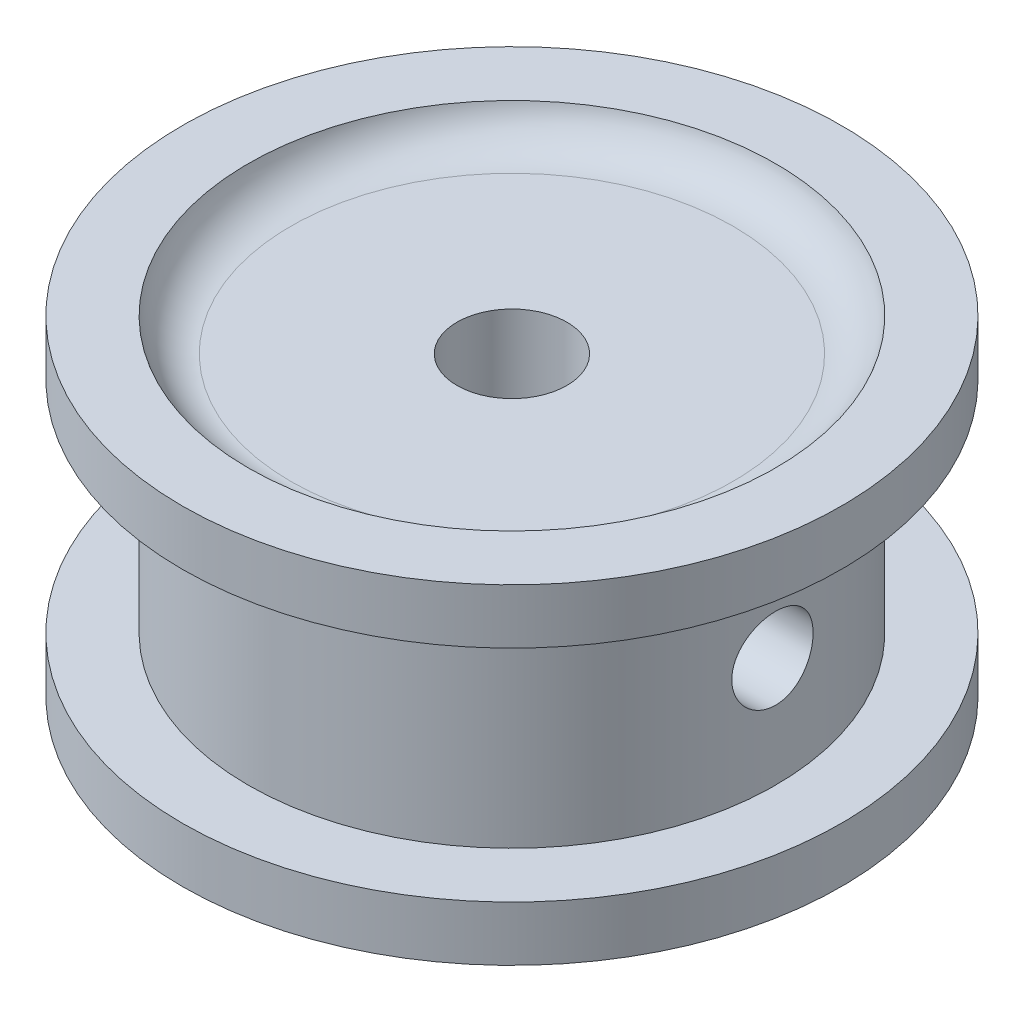
SolidWorks part; units mm, degrees
note: '?' marks a value the reader was unsure of. The reader was unsure of these and kept them because the rebuilt part matched: shared geometry of "Sketch1<11>".
ref_plane "Front Plane" through (0, 0, 0) normal (0, 0, 1) x (1, 0, 0)
ref_plane "Top Plane" through (0, 0, 0) normal (0, 1, 0) x (1, 0, 0)
ref_plane "Right Plane" through (0, 0, 0) normal (1, 0, 0) x (0, 0, -1)
sketch "Sketch1" plane through (0, 0, 0) normal (0, 1, 0) x (1, 0, 0)
  line L5 (0, -12) -> (0, -18.4476) construction
  arc A1 (12, 0) -> (0, 12) centre (0, 0) ccw
  arc A2 (15, 0) -> (0, 15) centre (0, 0) ccw
  arc A5 (0, -15) -> (15, 0) centre (0, 0) ccw
  arc A6 (0, -12) -> (12, 0) centre (0, 0) ccw
  arc A9 (-15, 0) -> (0, -15) centre (0, 0) ccw
  arc A10 (-12, 0) -> (0, -12) centre (0, 0) ccw
  arc A13 (0, 15) -> (-15, 0) centre (0, 0) ccw
  arc A14 (0, 12) -> (-12, 0) centre (0, 0) ccw
  point P57 (0, 0)
  dimension "D1" = 24
  dimension "D2" = 30
  dimension "D4" = 4
extrude "Boss-Extrude6" add sketch "Sketch1" along normal blind 6 contours A1 A14 A10 A6
extrude "Boss-Extrude7" add sketch "Sketch1<11>" against normal blind 1.5 and the other way blind 0.9958
sketch "Sketch1<11>" plane through (0, 0, 0) normal (0, 1, 0) x (1, 0, 0) same geometry as "Sketch1"
sketch "Sketch4" plane through (0, 6, 0) normal (0, 1, 0) x (1, 0, 0)
  circle A0 centre (0, 0) radius 2.5
  dimension "D1" = 5
fillet "Fillet17" radius 2 1 edges at (0, 0, 12)
extrude "Cut-Extrude2" cut sketch "Sketch4" against normal blind 11.5
ref_plane "Plane2" through (0, 6, 0) normal (0, 1, 0) x (1, 0, 0)
mirror "Mirror6" about plane through (0, 6, 0) normal (0, 1, 0) of bodies 110
ref_point "Point1"
ref_axis "Axis1" through (0, 6, 0) along (0, 1, 0)?
sketch "Sketch11" plane through (0, 0, 0) normal (1, 0, 0) x (0, 0, -1)
  circle A0 centre (0, 6) radius 1.4
  dimension "D1" = 2.8
extrude "Cut-Extrude3" cut sketch "Sketch11" against normal blind 15
ref_plane "Plane3" through (-3.5, 0, 0) normal (1, 0, 0) x (0, 0, -1)
sketch "Sketch12" plane through (-3.5, 0, 0) normal (1, 0, 0) x (0, 0, -1)
  line L1 (3.1754, 6) -> (1.5877, 8.75)
  line L2 (1.5877, 8.75) -> (-1.5877, 8.75)
  line L3 (-1.5877, 8.75) -> (-3.1754, 6)
  line L4 (-3.1754, 6) -> (-1.5877, 3.25)
  line L5 (-1.5877, 3.25) -> (1.5877, 3.25)
  line L6 (1.5877, 3.25) -> (3.1754, 6)
  circle A0 centre (0, 6) radius 2.75 construction
  dimension "D1" = 5.5
ref_axis "Axis2" through (-3.5, -2.25, 0) along (0, 1, 0)?
ref_axis "Axis3" through (-3.5, 6, 55) along (0, 0, -1)?
sketch "Sketch14" plane through (0, 0, 0) normal (0, -1, 0) x (1, 0, 0)
  line L0 (0, -3.25) -> (-6.8655, -3.25) construction
  line L2 (-6, 3.25) -> (-6, -3.25)
  line L6 (-3.5, -3.25) -> (-3.5, 3.25)
  line L7 (-3.5, -8.25) -> (-3.5, 8.25) construction
  line L8 (-3.5, 3.25) -> (-6, 3.25)
  line L9 (-6, -3.25) -> (-3.5, -3.25)
  circle A1 centre (0, 0) radius 2.5 construction
  point P10 (-3.5, 0)
  dimension "D1" = 3.25
  dimension "D2" = 2.5
  dimension "D3" = 6.5
extrude "Cut-Extrude10" cut sketch "Sketch12" against normal blind 2 and the other way blind 0.5
extrude "Cut-Extrude15" cut sketch "Sketch14" against normal blind 8.75
sketch "Sketch16" plane through (0, 0, 0) normal (1, 0, 0) x (0, 0, -1)
  line L0 (55, 6) -> (-55, 6) construction
  line L1 (0, 6) -> (0, 20.0007) construction
  circle A0 centre (0, 6) radius 1.85
  dimension "D1" = 3.7
extrude "Cut-Extrude16" cut sketch "Sketch16" along normal blind 15
